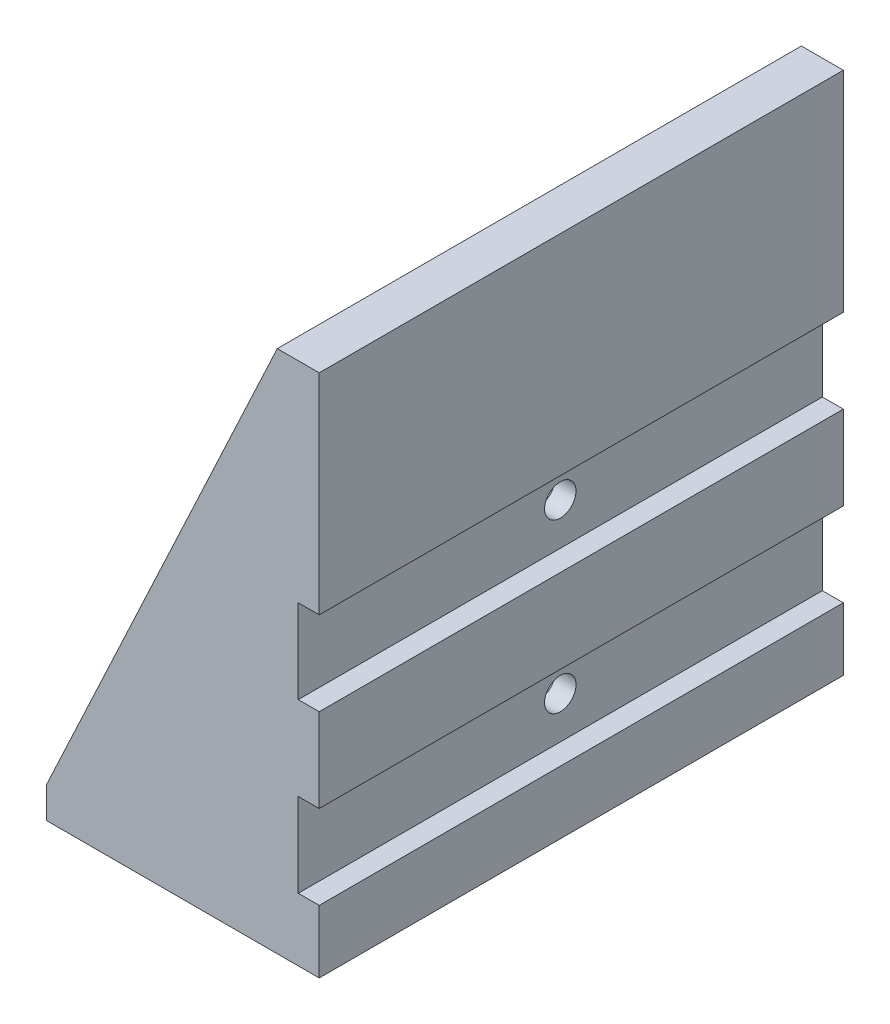
SolidWorks part; units mm, degrees
ref_plane "Front Plane" through (0, 0, 0) normal (0, 0, 1) x (1, 0, 0)
ref_plane "Top Plane" through (0, 0, 0) normal (0, 1, 0) x (1, 0, 0)
ref_plane "Right Plane" through (0, 0, 0) normal (1, 0, 0) x (0, 0, -1)
sketch "Sketch1" plane through (0, 0, 0) normal (0, 0, 1) x (1, 0, 0)
  line L0 (-13, 0) -> (13, 0)
  line L1 (-13, 0) -> (-13, 3)
  line L2 (-13, 3) -> (9, 50)
  line L3 (-13, 3) -> (20.3287, 3) construction
  line L4 (9, 50) -> (13, 50)
  line L5 (13, 0) -> (13, 50)
  point P4 (0, 0)
  dimension "D1" = 26
  dimension "D2" = 3
  dimension "D3" = 50
  dimension "D4" = 4
extrude "Boss-Extrude1" add sketch "Sketch1" along normal blind 50
sketch "Sketch2" plane through (13, 0, 0) normal (1, 0, 0) x (0, 0, -1)
  line L0 (-50, 0) -> (-50, 50) construction
  line L1 (-50, 14) -> (0, 14)
  line L2 (-50, 14) -> (-50, 6)
  line L3 (-50, 6) -> (0, 6)
  line L4 (0, 14) -> (0, 6)
  line L5 (0, 0) -> (0, 50) construction
  line L6 (-50, 0) -> (0, 0) construction
  line L8 (-50, 22) -> (0, 22)
  line L9 (-50, 22) -> (-50, 30)
  line L10 (-50, 30) -> (0, 30)
  line L11 (0, 22) -> (0, 30)
  dimension "D1" = 8
  dimension "D2" = 6
  dimension "D3" = 8
  dimension "D4" = 8
extrude "Cut-Extrude1" cut sketch "Sketch2" against normal blind 2
sketch "Sketch3" plane through (-11.8154, 5.5306, 0) normal (-0.9057, 0.4239, 0) x (0, 0, 1)
  line L0 (2.5, 49.1) -> (2.5, -2.7942)
  line L1 (2.5, -2.7942) -> (17.5, -2.7942)
  line L2 (17.5, -2.7942) -> (17.5, 49.1)
  line L4 (50, -2.7942) -> (0, -2.7942) construction
  line L5 (2.5, 49.1) -> (17.5, 49.1)
  line L6 (50, 49.1) -> (0, 49.1) construction
ref_plane "Plane1" through (-13, 0, 0) normal (-1, 0, 0) x (0, 0, 1)
sketch "Sketch4" plane through (-13, 0, 0) normal (-1, 0, 0) x (0, 0, 1)
  line L4 (2.5, 50) -> (2.5, 2.9986)
  line L5 (47.5, 2.9986) -> (47.5, 50)
  line L6 (2.5, 2.9986) -> (47.5, 2.9986)
  line L7 (2.5, 50) -> (47.5, 50)
  line L10 (50, 50) -> (0, 50) construction
  line L11 (50, 0) -> (0, 0) construction
  dimension "D1" = 2.5
  dimension "D2" = 2.5
  dimension "D3" = 2.9986
extrude "Cut-Extrude2" cut sketch "Sketch4" against normal up to vertex (22 mm away) up to point (9, 50, 2.5)
sketch "Sketch6" plane through (11, 0, 0) normal (1, 0, 0) x (0, 0, -1)
  line L0 (-50, 26) -> (0, 26) construction
  line L1 (-50, 30) -> (-50, 22) construction
  line L2 (0, 22) -> (0, 30) construction
  line L3 (-50, 10) -> (0, 10) construction
  line L4 (-50, 14) -> (-50, 6) construction
  line L5 (0, 6) -> (0, 14) construction
  circle A0 centre (-25, 26) radius 1.5
  circle A1 centre (-25, 10) radius 1.5
  dimension "D1" = 3
extrude "Cut-Extrude4" cut sketch "Sketch6" against normal up to surface (2 mm away) up to face at (9, 26.4993, 25)
sketch "Sketch7" plane through (0, 2.9986, 0) normal (0, 1, 0) x (1, 0, 0)
  line L0 (-13, -25) -> (9, -25) construction
  line L3 (-10, -25) -> (6, -25) construction
  line L4 (-10, -24) -> (6, -24)
  line L5 (-10, -26) -> (6, -26)
  line L7 (-13, 0) -> (13, 0) construction
  arc A0 (-10, -24) -> (-10, -26) centre (-10, -25) ccw
  arc A1 (6, -26) -> (6, -24) centre (6, -25) ccw
  point P8 (-2, -25)
  dimension "D1" = 1
  dimension "D3" = 3
  dimension "D2" = 3
  dimension "D4" = 25
extrude "Cut-Extrude5" cut sketch "Sketch7" against normal up to surface (2.9986 mm away) up to face at (0, 0, 25)
fillet "Fillet1" radius 5 3 edges at (9, 2.9986, 25) (-2, 2.9986, 47.5) (-2, 2.9986, 2.5)
